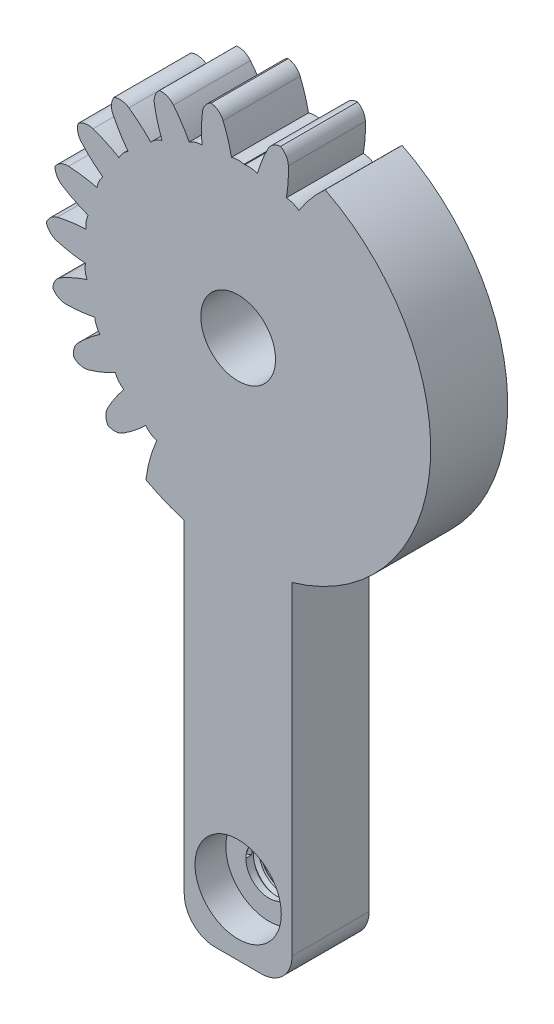
SolidWorks part; units mm, degrees
material "ABS"
ref_plane "Front Plane" through (0, 0, 0) normal (0, 0, 1) x (1, 0, 0)
ref_plane "Top Plane" through (0, 0, 0) normal (0, 1, 0) x (1, 0, 0)
ref_plane "Right Plane" through (0, 0, 0) normal (1, 0, 0) x (0, 0, -1)
sketch "Sketch1" plane through (0, 0, 0) normal (0, 0, 1) x (1, 0, 0)
  line L4 (0, 3.4732) -> (0, -24.3817) construction
  line L5 (-3.5, -12) -> (-3.5, -35)
  line L6 (3.5, -12) -> (3.5, -35)
  line L7 (-3.5, -35) -> (3.5, -35)
  circle A0 centre (0, 0) radius 12.5
  dimension "D1" = 25
  dimension "D2" = 3.5
  dimension "D3" = 23
extrude "Boss-Extrude2" add sketch "Sketch1" along normal blind 5
sketch "Sketch3" plane through (0, 0, 5) normal (0, 0, 1) x (1, 0, 0)
  circle A0 centre (0, 0) radius 2.425
  dimension "D1" = 4.85
extrude "Cut-Extrude1" cut sketch "Sketch3" against normal through all
sketch "Sketch6" plane through (0, 0, 5) normal (0, 0, 1) x (1, 0, 0)
  line L0 (0, -4.0834) -> (0, 15.1037) construction
  line L1 (0, 0) -> (1.3066, 12.4315) construction
  line L2 (0, 0) -> (0.5452, 12.4881) construction
  line L3 (0, 0) -> (-0.5452, 12.4881) construction
  line L4 (0, 0) -> (-1.3066, 12.4315) construction
  arc A0 (3.5, -12) -> (-3.5, -12) centre (0, 0) ccw construction
  arc A1 (1.3066, 12.4315) -> (-1.3066, 12.4315) centre (0, 0) ccw
  arc A2 (0.4338, 9.9359) -> (-0.4338, 9.9359) centre (0, 8.5) ccw
  arc A3 (0.4338, 9.9359) -> (1.3066, 12.4315) centre (9.7504, 8.078) cw
  arc A4 (-0.4338, 9.9359) -> (-1.3066, 12.4315) centre (-9.7504, 8.078) ccw
  point P13 (0, 12.5)
  dimension "D4" = 3
  dimension "D1" = 2.5
  dimension "D2" = 6
  dimension "D3" = 4
extrude "Cut-Extrude2" cut sketch "Sketch6" against normal through all
pattern_circular "CirPattern1" count 23 every 16.15 about axis through (0, 0, 0) along (0, 0, 1) skipping 10, 11, 12, 13, 14, 15, 16, 17, 18, 19, 20 of "Cut-Extrude2"
fillet "Fillet1" radius 2 2 edges at (3.5, -35, 2.5) (-3.5, -35, 2.5)
sketch "Sketch14" plane through (0, 0, 5) normal (0, 0, 1) x (1, 0, 0)
  line L0 (-1.5, -35) -> (1.5, -35) construction
  circle A0 centre (0, -31) radius 2.8
  dimension "D1" = 5.6
  dimension "D2" = 4
extrude "Cut-Extrude3" cut sketch "Sketch14" against normal blind 2
sketch "Sketch15" plane through (0, 0, 3) normal (0, 0, 1) x (1, 0, 0)
  circle A0 centre (0, -31) radius 1.5
  dimension "D1" = 3
extrude "Cut-Extrude4" cut sketch "Sketch15" against normal through all
thread "Thread1" pitch 0.5 start angle 0, offset 0, length 10, pitch 0.5, diameter 3
ref_plane "Plane2" through (-1.5, -31, 3) normal (0, -1, 0) x (-1, 0, 0)
sketch "Thread Profile2" plane through (-1.5, -31, 3) normal (0, -1, 0) x (-1, 0, 0)
  line L0 (0, 0) -> (0, 0.5) construction
  line L1 (0, 0) -> (0.2706, 0.1562)
  line L2 (0.2706, 0.1562) -> (0.2706, 0.2187)
  line L3 (0.2706, 0.2187) -> (0, 0.375)
  line L4 (0.2706, 0.1875) -> (0, 0.1875) construction
  line L11 (0, 0) -> (0, 0.375)
  point P2 (0, 0)
  dimension "Pitch" = 0.5
  dimension "Profile_Angle" = 60
  dimension "Profile_Land" = 0.0625
  dimension "Profile_Height" = 0.2706
fillet "Fillet8" radius 1 20 edges at (-8.143, -9.4838, 2.5) (-8.8079, -8.8696, 2.5) (-10.4596, -6.8445, 2.5) (-10.9275, -6.0697, 2.5) (-12.1845, -2.7906, 2.5) (-11.9506, -3.6651, 2.5) (-12.4985, -0.1963, 2.5) (-12.4799, 0.7087, 2.5) (-11.7903, 4.152, 2.5) (-12.0598, 3.2879, 2.5) (-10.6694, 6.5126, 2.5) (-10.1701, 7.2677, 2.5) (-7.7472, 9.8097, 2.5) (-8.4368, 9.2233, 2.5) (-4.7129, 11.5775, 2.5) (-5.5384, 11.2061, 2.5) (-2.2028, 12.3044, 2.5) (-1.3066, 12.4315, 2.5) (2.3208, 12.2827, 2.5) (3.2036, 12.0825, 2.5)
